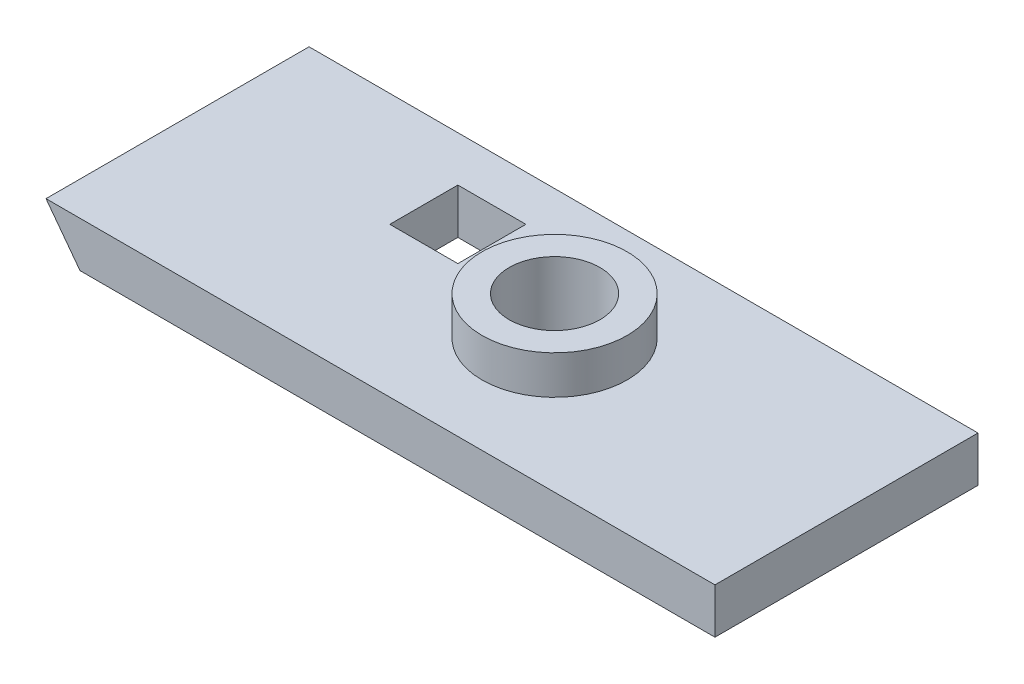
SolidWorks part; units mm, degrees
ref_plane "前视基准面" through (0, 0, 0) normal (0, 0, 1) x (1, 0, 0)
ref_plane "上视基准面" through (0, 0, 0) normal (0, 1, 0) x (1, 0, 0)
ref_plane "右视基准面" through (0, 0, 0) normal (1, 0, 0) x (0, 0, -1)
sketch "草图2" plane through (0, 0, 0) normal (0, 1, 0) x (1, 0, 0)
  line L1 (-30.1985, 7.2699) -> (-0.1985, 7.2699)
  line L2 (-30.1985, 7.2699) -> (-30.1985, -4.3301)
  line L3 (-30.1985, -4.3301) -> (-0.1985, -4.3301)
  line L4 (-0.1985, 7.2699) -> (-0.1985, -4.3301)
  line L5 (-32.1582, -4.3301) -> (-32.1582, 7.2699) construction
  line L7 (-0.1985, 1.4699) -> (-30.1985, 1.4699) construction
  line L9 (-34.0753, 7.2699) -> (0.3265, 7.2699) construction
  circle A1 centre (-15.1582, 1.5574) radius 2
  circle A2 centre (-15.1582, 1.5574) radius 3.2 construction
  circle A3 centre (-15.1582, 1.5574) radius 3.2 construction
  dimension "D4" = 4
  dimension "D5" = 6.4
  dimension "D1" = 30
extrude "凸台-拉伸1" add sketch "草图2" along normal blind 2
sketch "草图3" plane through (0, 2, 0) normal (0, 1, 0) x (1, 0, 0)
  circle A0 centre (-15.1582, 1.5574) radius 2
  circle A1 centre (-15.1582, 1.5574) radius 3.2
extrude "凸台-拉伸2" add sketch "草图3" along normal blind 1.7
sketch "草图4" plane through (0, 0, 0) normal (0, -1, 0) x (1, 0, 0)
  line L5 (-31.6367, 4.3301) -> (-31.6367, -7.2699) construction
  line L7 (-23.1367, -2.2699) -> (-20.1367, -2.2699)
  line L8 (-23.1367, -2.2699) -> (-23.1367, -5.2699)
  line L9 (-23.1367, -5.2699) -> (-20.1367, -5.2699)
  line L10 (-20.1367, -2.2699) -> (-20.1367, -5.2699)
  line L11 (-0.1985, -7.2699) -> (-30.1985, -7.2699) construction
  dimension "D1" = 3
  dimension "D3" = 5
  dimension "D2" = 8.5
extrude "切除-拉伸1" cut sketch "草图4" against normal blind 5
sketch "草图5" plane through (0, 0, -7.2699) normal (0, 0, -1) x (-1, 0, 0)
  line L0 (30.1985, 2) -> (30.1985, 0)
  line L1 (30.1985, 0) -> (31.6985, 2)
  line L2 (31.6985, 2) -> (30.1985, 2)
  line L6 (0.1985, 2) -> (30.1985, 2) construction
  line L7 (30.1985, 2) -> (30.1985, 0) construction
  point P4 (30.1985, 1)
  point P6 (30.1985, 2)
  point P8 (30.1985, 1)
  point P9 (30.1985, 1)
  point P11 (0, 0)
  point P14 (31.3941, 2)
  dimension "D1" = 1.5
extrude "凸台-拉伸3" add sketch "草图5" against normal up to surface (11.6 mm away) up to face at (-15.1985, 1, 4.3301)
sketch "草图6" plane through (0, 0, 0) normal (0, -1, 0) x (1, 0, 0)
  line L0 (-0.1985, -7.2699) -> (-30.1985, -7.2699) construction
  line L1 (-0.1985, 4.3301) -> (-2.1985, 4.3301)
  line L2 (-0.1985, 4.3301) -> (-0.1985, -7.2699)
  line L3 (-0.1985, -7.2699) -> (-2.1985, -7.2699)
  line L4 (-2.1985, 4.3301) -> (-2.1985, -7.2699)
  dimension "D1" = 2
extrude "切除-拉伸2" cut sketch "草图6" against normal through all
sketch "草图7" plane through (0, 0, -7.2699) normal (0, 0, -1) x (-1, 0, 0)
  line L0 (31.6985, 2) -> (30.1985, 0)
  line L1 (30.1985, 0) -> (29.586, 0)
  line L2 (2.1985, 0) -> (30.1985, 0) construction
  line L3 (29.586, 0) -> (31.086, 2)
  line L4 (2.1985, 2) -> (31.6985, 2) construction
  line L5 (31.086, 2) -> (31.6985, 2)
  dimension "D1" = 0.49
